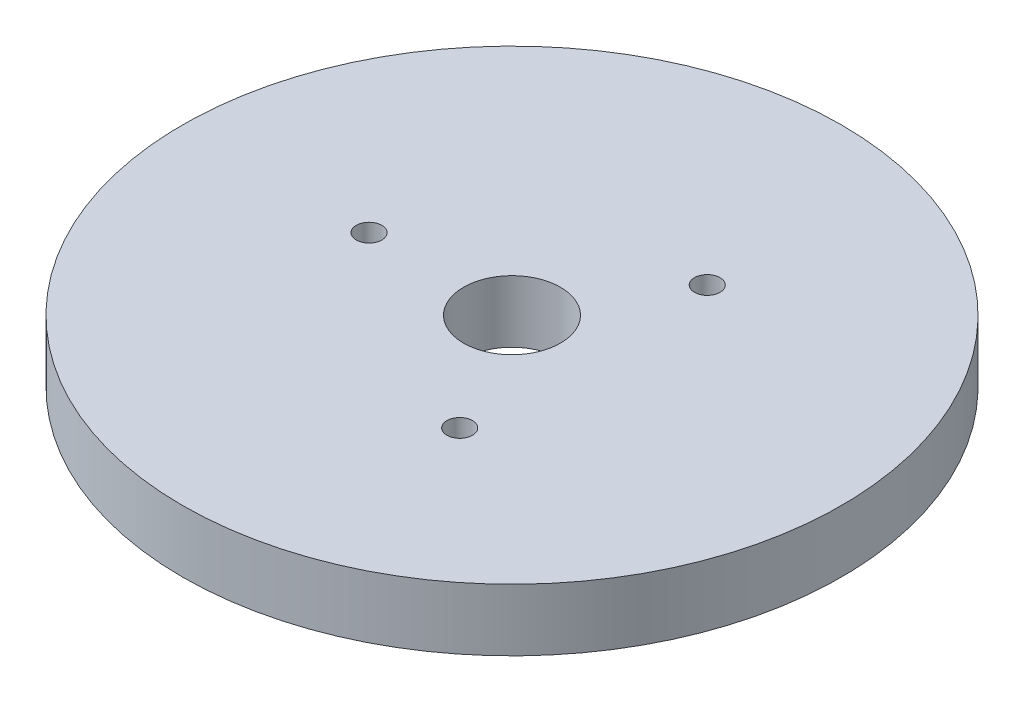
SolidWorks part; units mm, degrees
ref_plane "Front Plane" through (0, 0, 0) normal (0, 0, 1) x (1, 0, 0)
ref_plane "Top Plane" through (0, 0, 0) normal (0, 1, 0) x (1, 0, 0)
ref_plane "Right Plane" through (0, 0, 0) normal (1, 0, 0) x (0, 0, -1)
sketch "Sketch1" plane through (0, 0, 0) normal (0, 1, 0) x (1, 0, 0)
  circle A0 centre (0, 0) radius 85
  dimension "FLANGE_OD" = 170
extrude "Boss-Extrude1" add sketch "Sketch1" along normal blind 16
sketch "Sketch2" plane through (0, 0, 0) normal (0, 1, 0) x (1, 0, 0)
  circle A0 centre (0, 0) radius 12.5
  dimension "BORE_D" = 25
extrude "Cut-Extrude1" cut sketch "Sketch2" along normal through all
sketch "Sketch3" plane through (0, 16, 0) normal (0, 1, 0) x (1, 0, 0)
  circle A0 centre (0, 0) radius 36.8664 construction
  circle A1 centre (-36.8664, 0) radius 3.2947
  dimension "BOLT_D" = 6.5894
  dimension "BOLT_PCD" = 73.7328
extrude "Cut-Extrude2" cut sketch "Sketch3" against normal blind 12.9978
pattern_circular "CirPattern1" count 3 over 360 about axis through (0, 0, 0) along (0, 1, 0) of "Cut-Extrude2"
